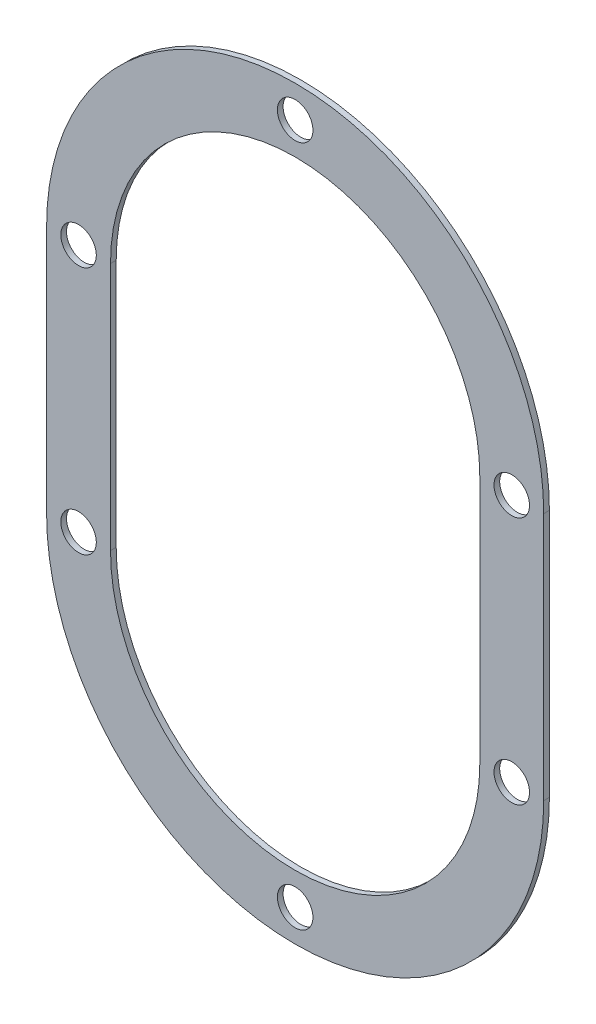
SolidWorks part; units mm, degrees
ref_plane "Front Plane" through (0, 0, 0) normal (0, 0, 1) x (1, 0, 0)
ref_plane "Top Plane" through (0, 0, 0) normal (0, 1, 0) x (1, 0, 0)
ref_plane "Right Plane" through (0, 0, 0) normal (1, 0, 0) x (0, 0, -1)
sketch "Sketch1" plane through (0, 0, 0) normal (0, 0, 1) x (1, 0, 0)
  line L0 (-35, 0) -> (-35, -35)
  line L1 (35, 0) -> (35, -35)
  line L2 (-26, 0) -> (-26, -35)
  line L3 (26, 0) -> (26, -35)
  line L4 (0, 35) -> (0, 26) construction
  line L5 (0, 26) -> (0, -61) construction
  line L6 (0, -61) -> (0, -70) construction
  line L7 (-35, 0) -> (-26, 0) construction
  line L8 (-35, -35) -> (-26, -35) construction
  line L9 (26, 0) -> (35, 0) construction
  line L10 (26, -35) -> (35, -35) construction
  arc A0 (35, 0) -> (-35, 0) centre (0, 0) ccw
  arc A1 (-35, -35) -> (35, -35) centre (0, -35) ccw
  arc A2 (26, 0) -> (-26, 0) centre (0, 0) ccw
  arc A3 (-26, -35) -> (26, -35) centre (0, -35) ccw
  circle A4 centre (0, 0) radius 30.5 construction
  circle A5 centre (0, -35) radius 30.5 construction
  circle A6 centre (-30.5, 0) radius 2.5
  circle A7 centre (0, 30.5) radius 2.5
  circle A8 centre (30.5, 0) radius 2.5
  circle A9 centre (30.5, -35) radius 2.5
  circle A10 centre (0, -65.5) radius 2.5
  circle A11 centre (-30.5, -35) radius 2.5
  point P15 (-30.5, 0)
  point P18 (-30.5, -35)
  dimension "D2" = 70
  dimension "D4" = 5
  dimension "D1" = 35
  dimension "D3" = 9
extrude "Boss-Extrude1" add sketch "Sketch1" along normal blind 0.8
